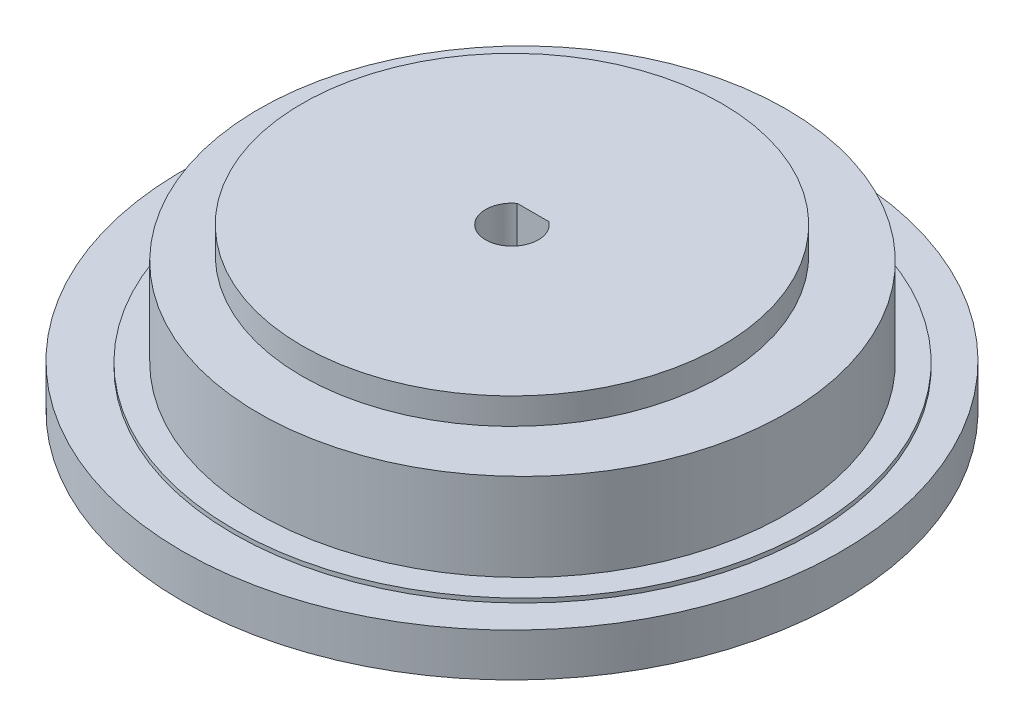
SolidWorks part; units mm, degrees
ref_plane "Front Plane" through (0, 0, 0) normal (0, 0, 1) x (1, 0, 0)
ref_plane "Top Plane" through (0, 0, 0) normal (0, 1, 0) x (1, 0, 0)
ref_plane "Right Plane" through (0, 0, 0) normal (1, 0, 0) x (0, 0, -1)
sketch "Sketch1" plane through (0, 0, 0) normal (0, 1, 0) x (1, 0, 0)
  line L1 (-2.5, 2) -> (0.5, 2)
  circle A0 centre (0, 0) radius 25
  arc A2 (-2.5, 2) -> (0.5, 2) centre (-1, 0) ccw
  point P7 (-1, -2.5)
  dimension "D1" = 5
  dimension "D2" = 50
  dimension "D3" = 1
  dimension "D4" = 4.5
extrude "Boss-Extrude1" add sketch "Sketch1" along normal blind 10.8
sketch "Sketch2" plane through (0, 0, 0) normal (0, -1, 0) x (1, 0, 0)
  circle A0 centre (-1, 0) radius 31.25
  circle A3 centre (-1, 0) radius 2.5 construction
  circle A4 centre (-1, 0) radius 2.5
  dimension "D1" = 62.5
extrude "Boss-Extrude2" add sketch "Sketch2" along normal blind 2
sketch "Sketch3" plane through (0, -2, 0) normal (0, -1, 0) x (1, 0, 0)
  circle A0 centre (-1, 0) radius 31.25 construction
  circle A1 centre (-1, 0) radius 31.25
  circle A2 centre (-1, 0) radius 30.1
  circle A3 centre (-1, 0) radius 19.9
  circle A6 centre (-1, 0) radius 2.5 construction
  circle A7 centre (-1, 0) radius 2.5
  circle M2 centre (-1, 0) radius 31.25
  dimension "D2" = 39.8
  dimension "D1" = 60.2
extrude "Boss-Extrude3" add sketch "Sketch3" along normal blind 2.5 contours A3 | A2 M2 region at (-31.3661, -2, 0) region at (-20.3371, -2, 0)
sketch "Sketch4" plane through (0, 0, 0) normal (0, 1, 0) x (1, 0, 0)
  circle A0 centre (0, 0) radius 25 construction
  circle A1 centre (0, 0) radius 25 construction
  circle A2 centre (0, 0) radius 27.4
  circle A3 centre (-1, 0) radius 31.25 construction
  circle A4 centre (-1, 0) radius 31.25
  dimension "D1" = 2.4
extrude "Cut-Extrude1" cut sketch "Sketch4" against normal blind 0.4
sketch "Sketch5" plane through (0, 10.8, 0) normal (0, 1, 0) x (1, 0, 0)
  circle A0 centre (-1, 0) radius 19.9
  circle A1 centre (0, 0) radius 25 construction
  circle A2 centre (0, 0) radius 25
  dimension "D1" = 39.8
extrude "Cut-Extrude2" cut sketch "Sketch5" against normal blind 2.5
